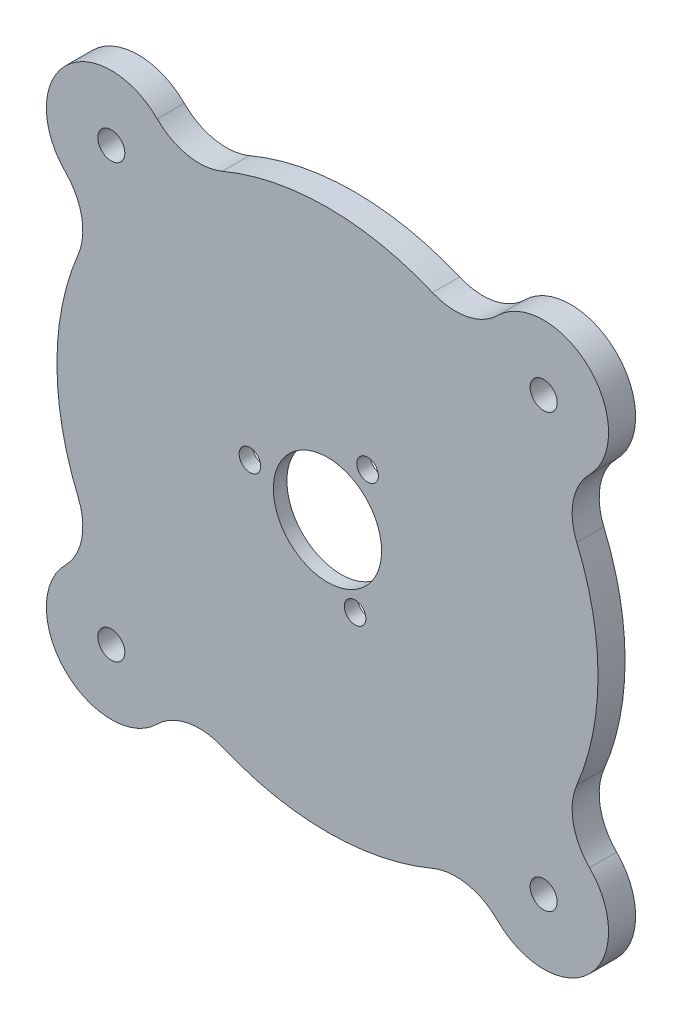
SolidWorks part; units mm, degrees
ref_plane "Front Plane" through (0, 0, 0) normal (0, 0, 1) x (1, 0, 0)
ref_plane "Top Plane" through (0, 0, 0) normal (0, 1, 0) x (1, 0, 0)
ref_plane "Right Plane" through (0, 0, 0) normal (1, 0, 0) x (0, 0, -1)
sketch "Sketch1" plane through (0, 0, 0) normal (0, 0, 1) x (1, 0, 0)
  line L13 (0, 100) -> (0, 50) construction
  line L19 (-76.3675, 76.3675) -> (-79.9031, 79.9031) construction
  line L28 (79.9031, -79.9031) -> (76.3675, -76.3675) construction
  line L29 (79.9031, -79.9031) -> (76.3675, -76.3675) construction
  line L30 (76.3675, 76.3675) -> (79.9031, 79.9031) construction
  line L31 (-79.9031, -79.9031) -> (-76.3675, -76.3675) construction
  line L34 (76.3675, 76.3675) -> (79.9031, 79.9031) construction
  line L36 (-76.3675, 76.3675) -> (-79.9031, 79.9031) construction
  line L37 (-79.9031, -79.9031) -> (-76.3675, -76.3675) construction
  arc A28 (62.9325, 96.8736) -> (38.827, 92.1546) centre (47.3715, 112.4346) cw
  arc A29 (-96.8736, 62.9325) -> (-92.1546, 38.827) centre (-112.4346, 47.3715) cw
  circle A30 centre (-79.9031, 79.9031) radius 5
  arc A31 (-96.8736, -62.9325) -> (-62.9325, -96.8736) centre (-79.9031, -79.9031) ccw
  arc A32 (-38.827, -92.1546) -> (38.827, -92.1546) centre (0, 0) ccw
  arc A33 (96.8736, -62.9325) -> (92.1546, -38.827) centre (112.4346, -47.3715) cw
  arc A34 (62.9325, -96.8736) -> (38.827, -92.1546) centre (47.3715, -112.4346) ccw
  arc A35 (-62.9325, -96.8736) -> (-38.827, -92.1546) centre (-47.3715, -112.4346) cw
  arc A36 (92.1546, -38.827) -> (92.1546, 38.827) centre (0, 0) ccw
  arc A37 (96.8736, -62.9325) -> (62.9325, -96.8736) centre (79.9031, -79.9031) cw
  circle A38 centre (-79.9031, -79.9031) radius 5
  arc A39 (-62.9325, 96.8736) -> (-38.827, 92.1546) centre (-47.3715, 112.4346) ccw
  circle A40 centre (79.9031, 79.9031) radius 5
  arc A41 (38.827, 92.1546) -> (-38.827, 92.1546) centre (0, 0) ccw
  arc A42 (96.8736, 62.9325) -> (62.9325, 96.8736) centre (79.9031, 79.9031) ccw
  arc A43 (-96.8736, 62.9325) -> (-62.9325, 96.8736) centre (-79.9031, 79.9031) cw
  arc A44 (96.8736, 62.9325) -> (92.1546, 38.827) centre (112.4346, 47.3715) ccw
  arc A45 (-92.1546, 38.827) -> (-92.1546, -38.827) centre (0, 0) ccw
  arc A46 (-96.8736, -62.9325) -> (-92.1546, -38.827) centre (-112.4346, -47.3715) ccw
  circle A47 centre (79.9031, -79.9031) radius 5
  circle A48 centre (-28.6596, 4.8019) radius 4 construction
  circle A49 centre (10.2143, -24.5395) radius 4 construction
  circle A50 centre (14.823, 23.4645) radius 4 construction
  circle A51 centre (-28.6596, 4.8019) radius 4
  circle A52 centre (10.2143, -24.5395) radius 4
  circle A53 centre (14.823, 23.4645) radius 4
  point P5 (0, 0)
  point P14 (0, 0)
  point P39 (0, 0)
  point P48 (23.6858, 23.6858)
  point P54 (0, 0)
  point P60 (23.6858, -23.6858)
  point P69 (-23.6858, -23.6858)
  point P78 (-23.6858, 23.6858)
  point P83 (0, 0)
  point P91 (47.3715, 47.3715)
  point P94 (47.3715, -47.3715)
  point P97 (-47.3715, -47.3715)
  point P101 (-47.3715, 47.3715)
  point P102 (0, 0)
extrude "Boss-Extrude1" add sketch "Sketch1" along normal blind 10
sketch "Sketch3" plane through (0, 0, 0) normal (0, 0, 1) x (1, 0, 0)
  line L0 (0, 51.6174) -> (0, -24.2463) construction
  line L1 (41.6698, 0) -> (-41.6698, 0) construction
  line L2 (0, 64.4859) -> (0, -24.2463) construction
  line L3 (59.526, 0) -> (-59.526, 0) construction
  line L4 (0, -42.9258) -> (0, -51.6174) construction
  line L5 (0, -42.9258) -> (0, -64.4859) construction
  circle A5 centre (0.5001, -0.4287) radius 42.5
  circle A8 centre (0, 0) radius 20
  point P8 (0.5001, -0.4287)
  point P11 (0, 0)
  point P14 (0, 0)
  point P17 (0.5001, -0.4287)
  point P18 (0, 0)
  point P21 (0, 0)
  point P22 (-0.7062, 0.1923)
  point P29 (-0.7062, 0.1923)
  dimension "D2" = 40
  dimension "D3" = 85
extrude "Cut-Extrude4" cut sketch "Sketch3" along normal through all both and the other way through all contours A8 region at (0, 0, 0)
sketch "Sketch6" plane through (0, 0, 0) normal (0, 0, 1) x (1, 0, 0)
  circle A0 centre (-0.9198, 0.7503) radius 42.5
extrude "Cut-Extrude5" cut sketch "Sketch6" along normal blind 5
